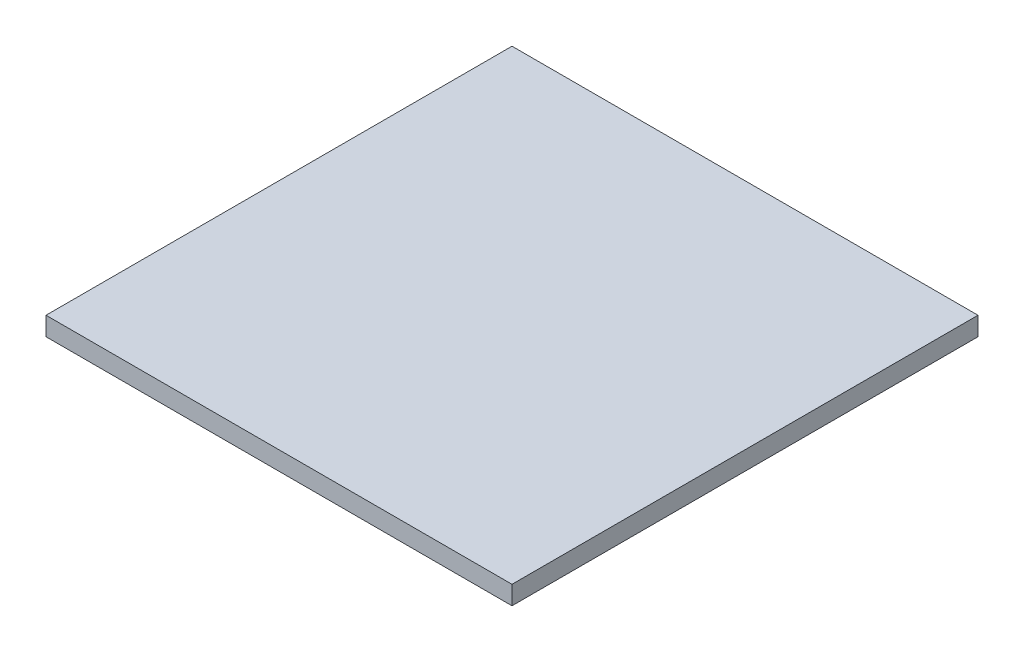
SolidWorks part; units mm, degrees
material "Pine"
ref_plane "Front" through (0, 0, 0) normal (0, 0, 1) x (1, 0, 0)
ref_plane "Top" through (0, 0, 0) normal (0, 1, 0) x (1, 0, 0)
ref_plane "Right" through (0, 0, 0) normal (1, 0, 0) x (0, 0, -1)
sketch "Sketch1" plane through (0, 0, 0) normal (0, 1, 0) x (1, 0, 0)
  line L1 (-37.5, -37.5) -> (37.5, -37.5)
  line L2 (-37.5, -37.5) -> (-37.5, 37.5)
  line L3 (-37.5, 37.5) -> (37.5, 37.5)
  line L4 (37.5, -37.5) -> (37.5, 37.5)
  line L5 (-37.5, -37.5) -> (37.5, 37.5) construction
  line L6 (-37.5, 37.5) -> (37.5, -37.5) construction
  point P0 (0, 0)
  dimension "D1" = 75
  dimension "D2" = 75
extrude "Boss-Extrude1" add sketch "Sketch1" along normal blind 3
